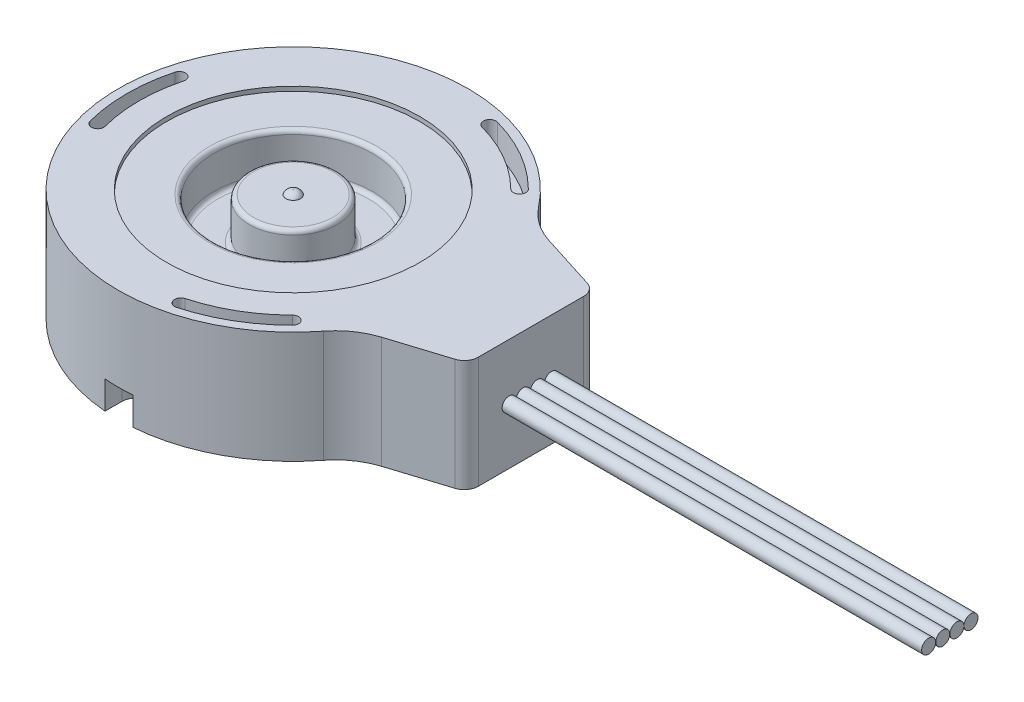
SolidWorks part; units mm, degrees
ref_plane "Front Plane" through (0, 0, 0) normal (0, 0, 1) x (1, 0, 0)
ref_plane "Top Plane" through (0, 0, 0) normal (0, 1, 0) x (1, 0, 0)
ref_plane "Right Plane" through (0, 0, 0) normal (1, 0, 0) x (0, 0, -1)
sketch "Sketch1" plane through (0, 0, 0) normal (0, 1, 0) x (1, 0, 0)
  line L0 (0, 12.5) -> (0, -12.5) construction
  line L1 (12.2974, 5.9875) -> (16.3016, 4.7209)
  line L2 (17, 3.7675) -> (17, -3.7675)
  line L3 (16.3016, -4.7209) -> (12.2974, -5.9875)
  line L4 (0, 0) -> (17, 0) construction
  arc A0 (9.8609, 7.6819) -> (9.8609, -7.6819) centre (0, 0) ccw
  arc A1 (12.2974, -5.9875) -> (9.8609, -7.6819) centre (13.8053, -10.7547) ccw
  arc A2 (12.2974, 5.9875) -> (9.8609, 7.6819) centre (13.8053, 10.7547) cw
  arc A3 (16.3016, 4.7209) -> (17, 3.7675) centre (16, 3.7675) cw
  arc A4 (17, -3.7675) -> (16.3016, -4.7209) centre (16, -3.7675) cw
  point P11 (10.6771, -6.5)
  point P14 (10.6771, 6.5)
  point P17 (17, 4.5)
  point P20 (17, -4.5)
  dimension "D1" = 25
  dimension "D5" = 5
  dimension "D6" = 1
  dimension "D2" = 9
  dimension "D3" = 17
  dimension "D4" = 13
extrude "Boss-Extrude1" add sketch "Sketch1" along normal blind 8
sketch "Sketch2" plane through (0, 0, 0) normal (0, -1, 0) x (1, 0, 0)
  line L0 (-12.5, 0) -> (0, 0) construction
  line L1 (0, 0) -> (0, 3.649) construction
  line L2 (1, 11.25) -> (1, 12.4599)
  line L3 (-11.25, -1) -> (-12.4599, -1)
  line L4 (-1, 11.25) -> (-1, 12.4599)
  line L5 (-11.25, 1) -> (-12.4599, 1)
  line L6 (1, -11.25) -> (1, -12.4599)
  line L7 (-1, -11.25) -> (-1, -12.4599)
  arc A1 (-1, 11.25) -> (1, 11.25) centre (0, 11.25) ccw
  arc A2 (9.8609, 7.6819) -> (9.8609, -7.6819) centre (0, 0) ccw construction
  arc A3 (1, 12.4599) -> (-1, 12.4599) centre (0, 0) ccw
  arc A4 (-12.4599, 1) -> (-12.4599, -1) centre (0, 0) ccw
  arc A5 (-11.25, -1) -> (-11.25, 1) centre (-11.25, 0) ccw
  arc A6 (-1, -12.4599) -> (1, -12.4599) centre (0, 0) ccw
  arc A7 (1, -11.25) -> (-1, -11.25) centre (0, -11.25) ccw
  point P4 (0, 12.5)
  point P29 (0, 0)
  dimension "D1" = 1
  dimension "D2" = 1.25
  dimension "D3" = 3
extrude "Cut-Extrude1" cut sketch "Sketch2" against normal blind 2
sketch "Sketch3" plane through (0, 0, 0) normal (0, 0, 1) x (1, 0, 0)
  line L0 (16, 0) -> (14.3396, 3.617)
  line L1 (16.3016, 0) -> (12.2974, 0) construction
  line L2 (14.1578, 3.617) -> (12.4974, 0)
  line L3 (17, 8) -> (17, 0) construction
  line L4 (12.2974, 8) -> (12.2974, 0) construction
  line L5 (14.2487, 3.815) -> (14.2487, 1.5378) construction
  line L6 (12.4974, 0) -> (16, 0)
  arc A0 (14.3396, 3.617) -> (14.1578, 3.617) centre (14.2487, 3.5753) ccw
  dimension "D3" = 0.1
  dimension "D1" = 1
  dimension "D2" = 0.2
extrude "Cut-Extrude2" cut sketch "Sketch3" against normal blind 1 and the other way blind 1
sketch "Sketch5" plane through (0, 0, 0) normal (1, 0, 0) x (0, 0, -1)
  line L0 (0, 0) -> (0, 11.717) construction
sketch "Sketch6" plane through (0, 0, 0) normal (0, 0, 1) x (1, 0, 0)
  line L15 (9.8609, 4) -> (1.9181, 4) construction
  line L17 (-9.0499, 8) -> (-0.0238, 8)
  line L18 (-9.0499, 7.688) -> (-9.0499, 8)
  line L19 (-5.9816, 7.688) -> (-9.0499, 7.688)
  line L20 (-5.6816, 5.0338) -> (-5.6816, 7.388)
  line L21 (-3.4343, 4.7338) -> (-5.3816, 4.7338)
  line L22 (-3.1343, 7.388) -> (-3.1343, 5.0338)
  line L23 (-0.5161, 7.688) -> (-2.8343, 7.688)
  arc A5 (-0.0238, 8) -> (-0.5161, 7.688) centre (-0.0238, 7.4555) ccw
  arc A6 (-5.6816, 7.388) -> (-5.9816, 7.688) centre (-5.9816, 7.388) ccw
  arc A7 (-5.3816, 4.7338) -> (-5.6816, 5.0338) centre (-5.3816, 5.0338) cw
  arc A8 (-3.1343, 5.0338) -> (-3.4343, 4.7338) centre (-3.4343, 5.0338) cw
  arc A9 (-2.8343, 7.688) -> (-3.1343, 7.388) centre (-2.8343, 7.388) ccw
revolve "Cut-Revolve3" cut sketch "Sketch6" angle 360 about L0
sketch "Sketch7" plane through (17, 0, 0) normal (1, 0, 0) x (0, 0, -1)
  line L0 (-3.7675, 4) -> (3.7675, 4) construction
  line L1 (-3.7675, 8) -> (-3.7675, 0) construction
  line L2 (3.7675, 8) -> (3.7675, 0) construction
  circle A0 centre (-1.5634, 4) radius 0.5
  circle A1 centre (-0.5534, 4) radius 0.5
  circle A2 centre (0.4566, 4) radius 0.5
  circle A3 centre (1.4666, 4) radius 0.5
  dimension "D1" = 1
  dimension "D2" = 1.01
  dimension "D3" = 1.01
  dimension "D4" = 1.01
extrude "Boss-Extrude4" add sketch "Sketch7" along normal blind 30
sketch "Sketch8" plane through (0, 8, 0) normal (0, 1, 0) x (1, 0, 0)
  line L0 (0, 0) -> (-21.3455, 0) construction
  arc A0 (-11.4966, -3.034) -> (-11.4973, 3.0315) centre (0, 0) cw
  arc A1 (-10.6378, -2.8022) -> (-10.6372, 2.8047) centre (0, 0) cw
  arc A2 (-11.4973, 3.0315) -> (-10.6372, 2.8047) centre (-11.0672, 2.9181) cw
  arc A3 (-11.4966, -3.034) -> (-10.6378, -2.8022) centre (-11.0672, -2.9181) ccw
  arc A4 (3.1208, 11.4734) -> (8.374, 8.4412) centre (0, 0) cw
  arc A5 (2.8921, 10.6137) -> (7.7475, 7.8097) centre (0, 0) cw
  arc A6 (3.1208, 11.4734) -> (2.8921, 10.6137) centre (3.0065, 11.0435) ccw
  arc A7 (8.374, 8.4412) -> (7.7475, 7.8097) centre (8.0607, 8.1255) cw
  arc A8 (8.3758, -8.4394) -> (3.1233, -11.4727) centre (0, 0) cw
  arc A9 (7.7457, -7.8115) -> (2.8897, -10.6144) centre (0, 0) cw
  arc A10 (8.3758, -8.4394) -> (7.7457, -7.8115) centre (8.0607, -8.1255) ccw
  arc A11 (3.1233, -11.4727) -> (2.8897, -10.6144) centre (3.0065, -11.0435) cw
  point P24 (0, 0)
  dimension "D1" = 3
extrude "Cut-Extrude3" cut sketch "Sketch8" against normal blind 2
